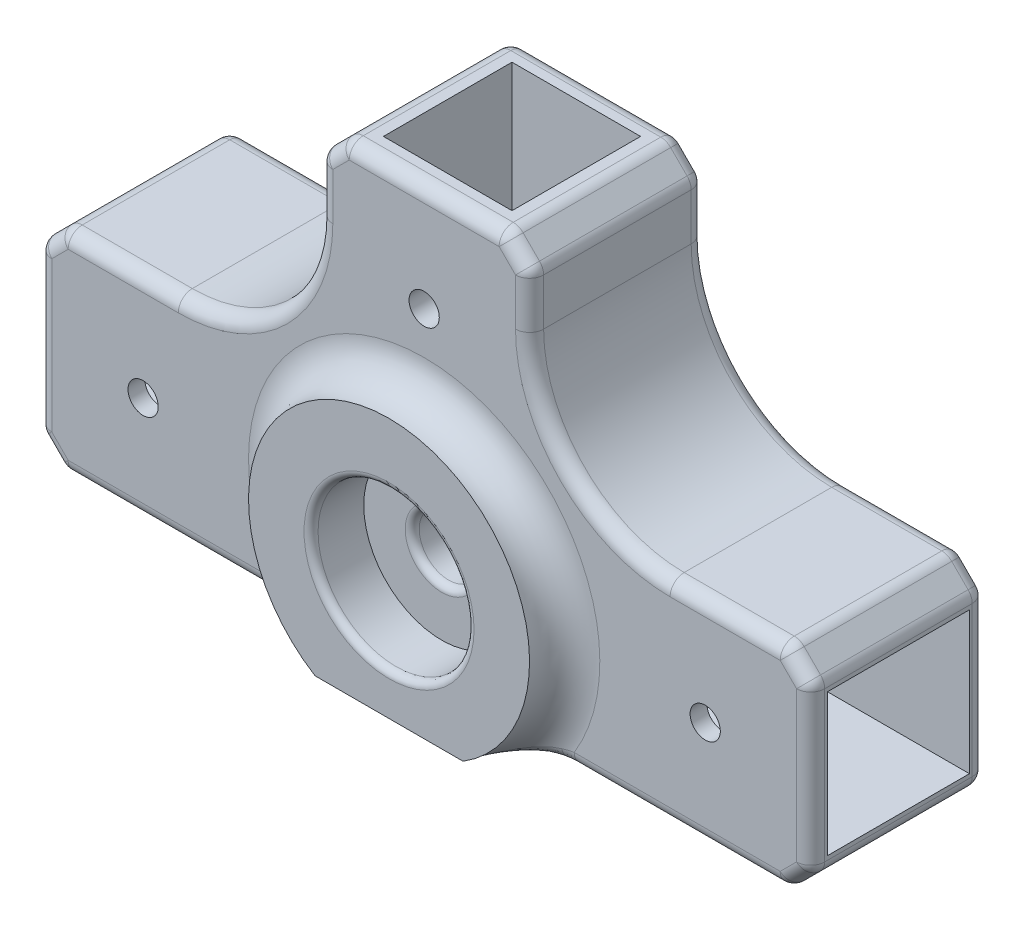
SolidWorks part; units mm, degrees
ref_plane "Alzado" through (0, 0, 0) normal (0, 0, 1) x (1, 0, 0)
ref_plane "Planta" through (0, 0, 0) normal (0, 1, 0) x (1, 0, 0)
ref_plane "Vista lateral" through (0, 0, 0) normal (1, 0, 0) x (0, 0, -1)
sketch "Croquis1" plane through (0, 0, 0) normal (0, 0, 1) x (1, 0, 0)
  circle A0 centre (0, 0) radius 20
  circle A1 centre (0, 0) radius 4.2
  dimension "D1" = 40
  dimension "D2" = 8.4
extrude "Saliente-Extruir1" add sketch "Croquis1" along normal mid plane 35
sketch "Croquis2" plane through (0, 0, 0) normal (0, 0, 1) x (1, 0, 0)
  line L0 (-20, 0) -> (0, 0) construction
  line L1 (0, 0) -> (20, 0) construction
  line L2 (0, 0) -> (0, 20) construction
  line L3 (-13.2288, 15) -> (-13.2288, -15)
  line L4 (-15, 15) -> (-55, 15)
  line L5 (-55, 15) -> (-55, -15)
  line L6 (-55, -15) -> (-13.2288, -15)
  line L7 (-13.2288, 15) -> (13.2288, 15)
  line L8 (-15, 15) -> (-15, 46)
  line L9 (-15, 46) -> (15, 46)
  line L10 (15, 46) -> (15, 15)
  line L11 (55, 15) -> (55, -15)
  line L12 (15, 15) -> (55, 15)
  line L13 (13.2288, 15) -> (13.2288, -15)
  line L14 (55, -15) -> (13.2288, -15)
  circle A0 centre (0, 0) radius 20 construction
  point P11 (-13.2288, 0)
  point P16 (0, 15)
  point P23 (0, 46)
  dimension "D1" = 30
  dimension "D2" = 35
  dimension "D3" = 30
  dimension "D4" = 26
  dimension "D5" = 40
extrude "Saliente-Extruir2" add sketch "Croquis2" along normal mid plane 25
sketch "Croquis3" plane through (55, 0, 0) normal (1, 0, 0) x (0, 0, -1)
  line L1 (-10.1, 10.1) -> (10.1, 10.1)
  line L2 (-10.1, 10.1) -> (-10.1, -10.1)
  line L3 (-10.1, -10.1) -> (10.1, -10.1)
  line L4 (10.1, 10.1) -> (10.1, -10.1)
  line L5 (-10.1, 10.1) -> (10.1, -10.1) construction
  line L6 (-10.1, -10.1) -> (10.1, 10.1) construction
  point P0 (0, 0)
  dimension "D1" = 20.2
  dimension "D2" = 20.2
extrude "Cortar-Extruir1" cut sketch "Croquis3" against normal blind 35
sketch "Croquis4" plane through (-55, 0, 0) normal (-1, 0, 0) x (0, 0, 1)
  line L1 (-10.1, 10.1) -> (10.1, 10.1)
  line L2 (-10.1, 10.1) -> (-10.1, -10.1)
  line L3 (-10.1, -10.1) -> (10.1, -10.1)
  line L4 (10.1, 10.1) -> (10.1, -10.1)
  line L5 (-10.1, 10.1) -> (10.1, -10.1) construction
  line L6 (-10.1, -10.1) -> (10.1, 10.1) construction
  point P0 (0, 0)
  dimension "D1" = 20.2
  dimension "D2" = 20.2
extrude "Cortar-Extruir2" cut sketch "Croquis4" against normal blind 35
sketch "Croquis5" plane through (0, 46, 0) normal (0, 1, 0) x (1, 0, 0)
  line L1 (-9.15, 9.15) -> (9.15, 9.15)
  line L2 (-9.15, 9.15) -> (-9.15, -9.15)
  line L3 (-9.15, -9.15) -> (9.15, -9.15)
  line L4 (9.15, 9.15) -> (9.15, -9.15)
  line L5 (-9.15, 9.15) -> (9.15, -9.15) construction
  line L6 (-9.15, -9.15) -> (9.15, 9.15) construction
  point P0 (0, 0)
  dimension "D1" = 18.3
  dimension "D2" = 18.3
extrude "Cortar-Extruir3" cut sketch "Croquis5" against normal blind 35
sketch "Croquis6" plane through (0, 0, 0) normal (0, 0, 1) x (1, 0, 0)
  line L0 (-55, 0) -> (-40, 0) construction
  line L1 (-55, 15) -> (-55, -15) construction
  line L2 (-40, 0) -> (0, 0) construction
  line L3 (0, 0) -> (0, 31) construction
  line L4 (0, 31) -> (0, 46) construction
  line L5 (15, 46) -> (-15, 46) construction
  circle A0 centre (-40, 0) radius 2.15
  circle A1 centre (0, 31) radius 2.15
  circle A2 centre (40, 0) radius 2.15
  dimension "D3" = 4.3
  dimension "D4" = 4.3
  dimension "D1" = 15
  dimension "D2" = 15
extrude "Cortar-Extruir4" cut sketch "Croquis6" against normal through all both and the other way through all
sketch "Croquis7" plane through (0, 0, 17.5) normal (0, 0, 1) x (1, 0, 0)
  circle A0 centre (0, 0) radius 11.1
  dimension "D1" = 22.2
extrude "Cortar-Extruir5" cut sketch "Croquis7" against normal blind 7.5 and the other way through all
chamfer "Chaflán1" distance 3.5 angle 45 6 edges at (-55, -15, 0) (-55, 15, 0) (55, -15, 0) (55, 15, 0) (15, 46, 0) (-15, 46, 0)
fillet "Redondeo1" radius 20 4 edges at (-13.2288, -15, 0) (13.2288, -15, 0) (15, 15, 0) (-15, 15, 0)
fillet "Redondeo2" radius 5 2 edges at (0, 20, -12.5) (0, 20, 12.5)
fillet "Redondeo3" radius 2 54 edges at (-16.3761, -15.2246, -13.2538) (-16.3761, -15.2246, 13.2538) (16.3761, -15.2246, -13.2538) (16.3761, -15.2246, 13.2538) (-35.75, -15, -12.5) (-51.5, -15, 0) (-35.75, -15, 12.5) (-53.25, -13.25, -12.5) (-53.25, -13.25, 12.5) (-55, -11.5, 0) (-55, 0, -12.5) (-55, 11.5, 0) (-55, 0, 12.5) (-53.25, 13.25, -12.5) (-53.25, 13.25, 12.5) (-51.5, 15, 0) (-43.25, 15, -12.5) (-43.25, 15, 12.5) (-20.8579, 20.8579, -12.5) (-20.8579, 20.8579, 12.5) (-15, 38.75, -12.5) (-15, 42.5, 0) (-15, 38.75, 12.5) (-13.25, 44.25, -12.5) (-13.25, 44.25, 12.5) (-11.5, 46, 0) (0, 46, -12.5) (35.75, -15, -12.5) (11.5, 46, 0) (0, 46, 12.5) (13.25, 44.25, -12.5) (15, 38.75, -12.5) (51.5, -15, 0) (35.75, -15, 12.5) (53.25, -13.25, -12.5) (13.25, 44.25, 12.5) (15, 42.5, 0) (20.8579, 20.8579, -12.5) (55, -11.5, 0) (53.25, -13.25, 12.5) (55, 0, -12.5) (15, 38.75, 12.5) (43.25, 15, -12.5) (53.25, 13.25, -12.5) (55, 0, 12.5) (55, 11.5, 0) (20.8579, 20.8579, 12.5) (51.5, 15, 0) (53.25, 13.25, 12.5) (43.25, 15, 12.5)
fillet "Redondeo4" radius 1 3 edges at (4.2, 0, -17.5) (4.2, 0, 10) (11.1, 0, 17.5)
sketch "Croquis8" plane through (0, 0, 17.5) normal (0, 0, 1) x (1, 0, 0)
  line L0 (0, -20) -> (-15, -20)
  line L1 (-15, -20) -> (-15, -17)
  line L2 (-15, -17) -> (15, -17)
  line L3 (15, -20) -> (0, -20)
  line L4 (15, -20) -> (15, -17)
  arc A0 (-9.6825, -17.5) -> (9.6825, -17.5) centre (0, 0) ccw construction
  dimension "D1" = 3
  dimension "D2" = 30
extrude "Cortar-Extruir6" cut sketch "Croquis8" against normal through all both and the other way through all
